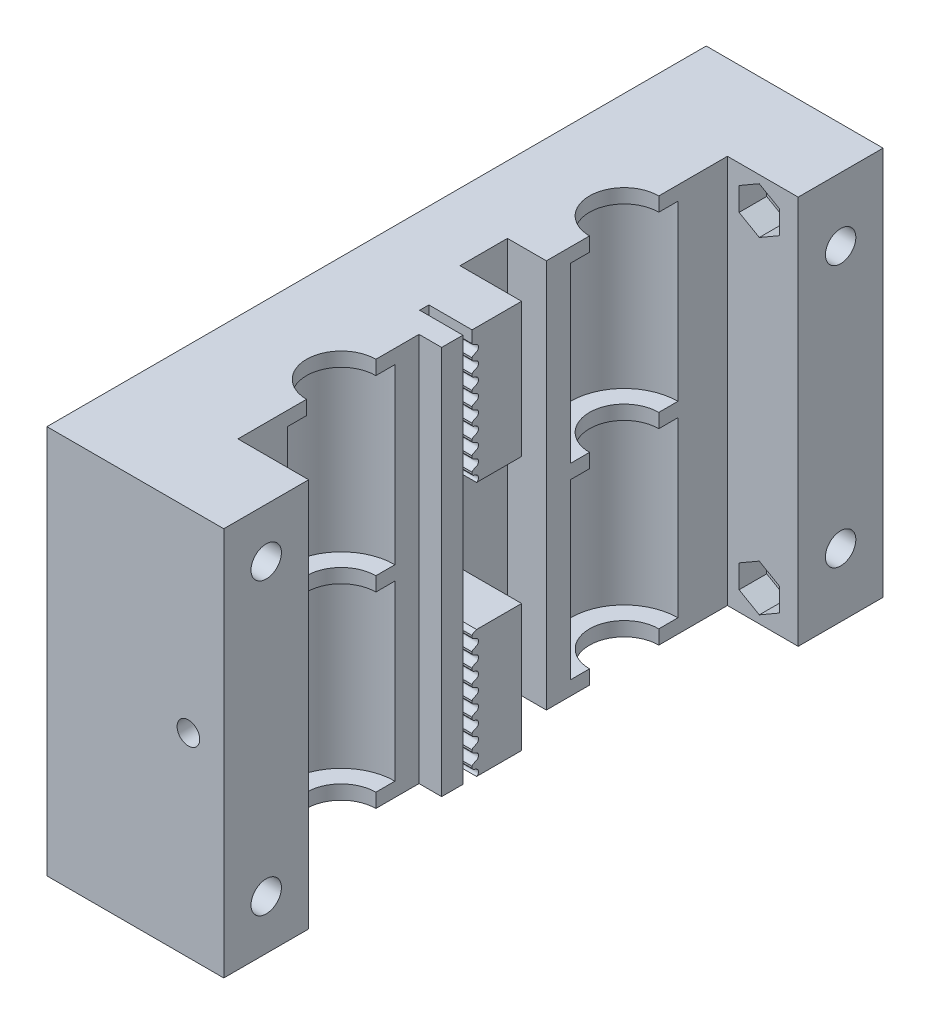
SolidWorks part; units mm, degrees
ref_plane "Front Plane" through (0, 0, 0) normal (0, 0, 1) x (1, 0, 0)
ref_plane "Top Plane" through (0, 0, 0) normal (0, 1, 0) x (1, 0, 0)
ref_plane "Right Plane" through (0, 0, 0) normal (1, 0, 0) x (0, 0, -1)
sketch "Sketch1" plane through (0, 0, 0) normal (0, 1, 0) x (1, 0, 0)
  line L0 (0, 36.6) -> (0, 43.6)
  line L1 (0, 43.6) -> (10, 43.6)
  line L2 (10, 43.6) -> (10, 55.6)
  line L3 (10, 55.6) -> (-15, 55.6)
  line L5 (-15, -37.6) -> (10, -37.6)
  line L6 (10, -37.6) -> (10, -25.6)
  line L7 (10, -25.6) -> (0, -25.6)
  line L8 (0, -25.6) -> (0, -18.6)
  line L9 (0, 21.4) -> (0, -3.4) construction
  line L10 (0, 18) -> (-5.5, 18)
  line L11 (-5.5, 18) -> (-5.5, 0)
  line L12 (-5.5, 0) -> (0, 0)
  line L24 (-15, 55.6) -> (-15, -37.6)
  line L25 (0, 0) -> (0, -3.4)
  line L26 (0, 18) -> (0, 21.4)
  arc A1 (0, 21.4) -> (0, 36.6) centre (0, 29) cw
  arc A2 (0, -18.6) -> (0, -3.4) centre (0, -11) cw
  dimension "D2" = 7.6
  dimension "D3" = 7.6
  dimension "D4" = 7
  dimension "D5" = 7
  dimension "D6" = 12
  dimension "D7" = 12
  dimension "D8" = 18
  dimension "D9" = 10
  dimension "D10" = 10
  dimension "D11" = 5.5
  dimension "D12" = 3.4
  dimension "D13" = 3.4
  dimension "D14" = 25
  dimension "D15" = 40
extrude "Boss-Extrude1" add sketch "Sketch1" along normal blind 55
sketch "Sketch2" plane through (0, 0, 0) normal (0, -1, 0) x (1, 0, 0)
  line L0 (0, 18.6) -> (0, 15.9)
  line L1 (0, 6.1) -> (0, 3.4)
  line L2 (0, -21.4) -> (0, -24.102)
  line L3 (0, -33.898) -> (0, -36.6)
  arc A0 (0, 3.4) -> (0, 18.6) centre (0, 11) cw
  arc A1 (0, 6.1) -> (0, 15.9) centre (0, 11) cw
  arc A2 (0, -36.6) -> (0, -21.4) centre (0, -29) cw
  arc A3 (0, -33.898) -> (0, -24.102) centre (0, -29) cw
  dimension "D1" = 4.9
  dimension "D2" = 4.898
extrude "Boss-Extrude2" add sketch "Sketch2" against normal blind 2
ref_plane "Plane1" through (0, 26.5, 0) normal (0, -1, 0) x (-1, 0, 0)
sketch "Sketch3" plane through (0, 26.5, 0) normal (0, -1, 0) x (-1, 0, 0)
  line L0 (0, -3.4) -> (0, -6.1)
  line L1 (0, -15.9) -> (0, -18.6)
  line L2 (0, 21.4) -> (0, 24.1)
  line L3 (0, 33.9) -> (0, 36.6)
  arc A0 (0, -18.6) -> (0, -3.4) centre (0, -11) ccw
  arc A1 (0, -15.9) -> (0, -6.1) centre (0, -11) ccw
  arc A2 (0, 36.6) -> (0, 21.4) centre (0, 29) cw
  arc A3 (0, 24.1) -> (0, 33.9) centre (0, 29) ccw
  dimension "D1" = 4.9
extrude "Boss-Extrude3" add sketch "Sketch3" against normal blind 2
ref_plane "Plane2" through (0, 53, 0) normal (0, -1, 0) x (-1, 0, 0)
sketch "Sketch4" plane through (0, 53, 0) normal (0, -1, 0) x (-1, 0, 0)
  line L0 (0, -18.6) -> (0, -15.9)
  line L1 (0, -6.1) -> (0, -3.4)
  line L2 (0, 36.6) -> (0, 33.9)
  line L3 (0, 24.1) -> (0, 21.4)
  arc A0 (0, -3.4) -> (0, -18.6) centre (0, -11) cw
  arc A1 (0, -15.9) -> (0, -6.1) centre (0, -11) ccw
  arc A2 (0, -15.9) -> (0, -6.1) centre (0, -11) ccw construction
  arc A3 (0, 21.4) -> (0, 36.6) centre (0, 29) ccw construction
  arc A5 (0, 24.1) -> (0, 33.9) centre (0, 29) ccw
  arc A6 (0, 21.4) -> (0, 36.6) centre (0, 29) ccw
  arc A7 (0, 24.1) -> (0, 33.9) centre (0, 29) ccw construction
extrude "Boss-Extrude4" add sketch "Sketch4" against normal blind 2
sketch "Sketch7" plane through (0, 55, 0) normal (0, 1, 0) x (1, 0, 0)
  line L0 (0, 0) -> (3.2, 0)
  line L1 (3.2, 0) -> (3.2, -2)
  line L2 (3.2, -2) -> (0, -2)
  line L3 (0, -6.1) -> (0, 0) construction
  line L4 (0, -2) -> (0, 0)
  dimension "D1" = 2
  dimension "D2" = 3.2
extrude "Boss-Extrude5" add sketch "Sketch7" against normal up to surface (55 mm away) up to face at (-0.6749, 0, -9)
sketch "Sketch8" plane through (0, 55, 0) normal (0, 1, 0) x (1, 0, 0)
  line L0 (0, 18) -> (0, 0) construction
  line L1 (-3.9424, 9) -> (6.0186, 9) construction
  line L2 (-5.5, 0) -> (3.2, 0)
  line L3 (3.2, 0) -> (-5.5, 0) construction
  line L4 (3.2, 0) -> (3.2, 3)
  line L5 (3.2, 3) -> (-5.5, 3)
  line L6 (-5.5, 0) -> (-5.5, 18) construction
  line L7 (-5.5, 3) -> (-5.5, 0)
  line L8 (3.2, -2) -> (3.2, 0) construction
  line L9 (-5.5, 11.3) -> (3.2, 11.3)
  line L10 (3.2, 11.3) -> (3.2, 4.3)
  line L11 (3.2, 4.3) -> (-5.5, 4.3)
  line L12 (-5.5, 4.3) -> (-5.5, 11.3)
  point P6 (0, 9)
  dimension "D1" = 3
  dimension "D2" = 7
  dimension "D3" = 1.3
extrude "Boss-Extrude6" add sketch "Sketch8" against normal up to surface (55 mm away) up to face at (-0.2443, 0, -7.7778)
sketch "Sketch11" plane through (3.2, 0, 0) normal (1, 0, 0) x (0, 0, -1)
  line L0 (1264.5675, 560.6102) -> (1262.5675, 560.6102) construction
  line L1 (4.3, 0) -> (4.3, 55) construction
  line L2 (4.2853, 45.4328) -> (4.2853, 47.4569)
  spline S0 degree 3 poles (4.2853, 47.4569) (4.284, 47.4147) (4.2867, 47.3463) (4.3158, 47.2523) (4.3712, 47.1708) (4.4771, 47.1012) (4.6041, 47.0544) (4.7214, 46.9971) (4.8254, 46.9474) (4.9241, 46.9047) (5.0186, 46.8525) (5.1086, 46.7783) (5.1561, 46.6816) (5.1905, 46.5926) (5.1913, 46.5195) (5.1931, 46.4561) (5.1891, 46.3829) (5.1871, 46.2871) (5.1399, 46.1709) (5.0494, 46.057) (4.9087, 45.9856) (4.7554, 45.916) (4.621, 45.8529) (4.5075, 45.8004) (4.4122, 45.7562) (4.3028, 45.6419) (4.2855, 45.5136) (4.2853, 45.4328) knots 0 0 0 0 0.042789 0.068472 0.09859 0.140403 0.193951 0.235463 0.272242 0.310543 0.344117 0.381404 0.42616 0.451184 0.477135 0.499165 0.515432 0.551275 0.595353 0.639476 0.695379 0.752126 0.810504 0.845135 0.878871 0.916023 1 1 1 1
  line M5 (4.3, 55) -> (4.3, 0)
  dimension "D1" = 2
extrude "Cut-Extrude4" cut sketch "Sketch11" against normal up to surface (8.7 mm away) contours S0 M5 region at (3.2, 46.4474, -4.673) up to face at (-5.5, 27.5, -3.65)
pattern_linear "LPattern1" count 24 spacing 2 along (0, -1, 0) count 4 spacing 2 along (0, 1, 0) of "Cut-Extrude4"
sketch "Sketch12" plane through (3.2, 0, 0) normal (1, 0, 0) x (0, 0, -1)
  line L0 (11.3, 0) -> (11.3, 55) construction
  line L1 (11.3, 36) -> (4.3, 36)
  line L2 (11.3, 36) -> (11.3, 18)
  line L3 (11.3, 18) -> (4.3, 18)
  line L4 (4.3, 36) -> (4.3, 18)
  dimension "D1" = 18
  dimension "D2" = 19
extrude "Cut-Extrude5" cut sketch "Sketch12" against normal up to surface (8.7 mm away) up to face at (-5.5, 27.5, -14.65)
sketch "Sketch13" plane through (0, 55, 0) normal (0, 1, 0) x (1, 0, 0)
  line L0 (-5.5, 3) -> (-2.9059, 3)
  line L1 (3.2, 3) -> (-5.5, 3) construction
  line L6 (-2.9059, 3) -> (-2.9059, 7.169)
  line L7 (-2.9059, 7.169) -> (-5.5, 7.169)
  line L8 (-5.5, 18) -> (-5.5, 0) construction
  line L9 (-5.5, 7.169) -> (-5.5, 3)
extrude "Boss-Extrude16" add sketch "Sketch13" against normal up to surface (55 mm away) up to face at (-0.409, 0, -8.1123)
sketch "Sketch14" plane through (0, 55, 0) normal (0, 1, 0) x (1, 0, 0)
  line L0 (0, 0) -> (0, -2)
  line L1 (0, -2) -> (3.2, -2)
  line L2 (3.2, -2) -> (3.2, 0)
  line L3 (3.2, -2) -> (3.2, 3) construction
  line L4 (3.2, 0) -> (0, 0)
extrude "Cut-Extrude6" cut sketch "Sketch14" against normal up to surface (55 mm away) up to face at (-0.1732, 0, -8.1123)
sketch "Sketch16" plane through (-2.9059, 0, 0) normal (1, 0, 0) x (0, 0, -1)
  line L0 (7.169, 36) -> (3, 36)
  line L1 (3, 0) -> (3, 55) construction
  line L2 (7.169, 18) -> (3, 18)
  line L3 (3, 18) -> (3, 36)
  line L4 (7.169, 36) -> (7.169, 18)
extrude "Cut-Extrude7" cut sketch "Sketch16" against normal up to surface (2.5941 mm away) up to face at (-5.5, 27.25, -11.9423)
sketch "Sketch17" plane through (-15, 0, 0) normal (-1, 0, 0) x (0, 0, 1)
  line L0 (-55.6, 55) -> (37.6, 55) construction
  line L1 (37.6, 55) -> (37.6, 0) construction
  line L2 (37.6, 0) -> (25.6, 0) construction
  line L3 (-36.6, 0) -> (-43.6, 0) construction
  line L4 (-55.6, 55) -> (-55.6, 0) construction
  circle A0 centre (31.6, 48) radius 2.15
  circle A1 centre (31.6, 7) radius 2.15
  circle A2 centre (-49.6, 9) radius 2.15
  circle A3 centre (-49.6, 46) radius 2.15
  dimension "D1" = 4.3
  dimension "D2" = 4.3
  dimension "D3" = 4.3
  dimension "D4" = 4.3
  dimension "D6" = 6
  dimension "D7" = 7
  dimension "D5" = 7
  dimension "D8" = 6
  dimension "D9" = 9
  dimension "D10" = 6
  dimension "D11" = 6
  dimension "D12" = 9
extrude "Cut-Extrude8" cut sketch "Sketch17" against normal up to surface (25 mm away) up to face at (10, 27.5, 31.6)
ref_plane "Plane3" through (-11.9, 0, 0) normal (-1, 0, 0) x (0, 0, 1)
sketch "Sketch20" plane through (-5.5, 0, 0) normal (1, 0, 0) x (0, 0, -1)
  line L0 (55.6, 55) -> (-37.6, 55) construction
  line L1 (55.6, 55) -> (55.6, 0) construction
  circle A0 centre (7, 27.5) radius 2.7
  dimension "D1" = 5.4
  dimension "D2" = 27.5
  dimension "D3" = 48.6
extrude "Cut-Extrude9" cut sketch "Sketch20" against normal up to surface (9.5 mm away) up to face at (-15, 46, -47.45)
sketch "Sketch21" plane through (0, 0, -43.6) normal (0, 0, 1) x (1, 0, 0)
  line L0 (10, 55) -> (10, 0) construction
  line L1 (4.5, 47.3091) -> (7.35, 48.9546)
  line L2 (7.35, 48.9546) -> (7.35, 52.2454)
  line L3 (7.35, 52.2454) -> (4.5, 53.8909)
  line L4 (4.5, 53.8909) -> (1.65, 52.2454)
  line L5 (1.65, 52.2454) -> (1.65, 48.9546)
  line L6 (1.65, 48.9546) -> (4.5, 47.3091)
  line L7 (0, 55) -> (10, 55) construction
  circle A0 centre (4.5, 50.6) radius 2.85 construction
  dimension "D2" = 4.4
  dimension "D3" = 5.5
  dimension "D1" = 5.7
ref_plane "Plane4" through (0, 27.5, 0) normal (0, 1, 0) x (1, 0, 0)
extrude "Cut-Extrude10" cut sketch "Sketch21" against normal blind 3.9
sketch "Sketch23" plane through (0, 0, -47.5) normal (0, 0, 1) x (1, 0, 0)
  line L0 (0, 55) -> (10, 55) construction
  line L1 (10, 55) -> (10, 0) construction
  circle A0 centre (4.5, 50.6) radius 1.6
  dimension "D1" = 3.2
  dimension "D2" = 4.4
  dimension "D3" = 5.5
extrude "Cut-Extrude11" cut sketch "Sketch23" against normal up to surface (8.1 mm away) up to face at (-2.5, 27.5, -55.6)
mirror "Mirror1" about plane through (0, 27.5, 0) normal (0, 1, 0) of "Cut-Extrude11", "Cut-Extrude10"
sketch "Sketch26" plane through (0, 0, 25.6) normal (0, 0, -1) x (-1, 0, 0)
  line L0 (-10, 55) -> (-10, 0) construction
  line L1 (-5, 24.2091) -> (-2.15, 25.8546)
  line L2 (-2.15, 25.8546) -> (-2.15, 29.1454)
  line L3 (-2.15, 29.1454) -> (-5, 30.7909)
  line L4 (-5, 30.7909) -> (-7.85, 29.1454)
  line L5 (-7.85, 29.1454) -> (-7.85, 25.8546)
  line L6 (-7.85, 25.8546) -> (-5, 24.2091)
  line L7 (-10, 0) -> (0, 0) construction
  circle A0 centre (-5, 27.5) radius 2.85 construction
  dimension "D1" = 27.5
  dimension "D2" = 5
  dimension "D3" = 5.7
extrude "Cut-Extrude12" cut sketch "Sketch26" against normal blind 4
sketch "Sketch27" plane through (0, 0, 29.6) normal (0, 0, -1) x (-1, 0, 0)
  line L0 (-10, 55) -> (-10, 0) construction
  line L1 (-10, 55) -> (0, 55) construction
  circle A0 centre (-5, 27.5) radius 1.6
  dimension "D3" = 3.2
  dimension "D1" = 5
  dimension "D2" = 27.5
extrude "Cut-Extrude13" cut sketch "Sketch27" against normal up to surface (8 mm away) up to face at (-2.5, 27.5, 37.6)
sketch "Sketch28" plane through (-15, 0, 0) normal (-1, 0, 0) x (0, 0, 1)
  line L0 (-55.6, 55) -> (-55.6, 0) construction
  line L1 (-45.95, 11.1073) -> (-49.6, 13.2147)
  line L2 (-49.6, 13.2147) -> (-53.25, 11.1073)
  line L3 (-53.25, 11.1073) -> (-53.25, 6.8927)
  line L4 (-53.25, 6.8927) -> (-49.6, 4.7853)
  line L5 (-49.6, 4.7853) -> (-45.95, 6.8927)
  line L6 (-45.95, 6.8927) -> (-45.95, 11.1073)
  circle A0 centre (-49.6, 9) radius 3.65 construction
  dimension "D1" = 7.3
extrude "Cut-Extrude14" cut sketch "Sketch28" against normal blind 4
pattern_linear "LPattern4" count 2 spacing 37 along (0, 1, 0) of "Cut-Extrude14"
sketch "Sketch29" plane through (-15, 0, 0) normal (-1, 0, 0) x (0, 0, 1)
  line L0 (37.6, 55) -> (37.6, 0) construction
  line L1 (31.6, 11.2147) -> (27.95, 9.1073)
  line L2 (27.95, 9.1073) -> (27.95, 4.8927)
  line L3 (27.95, 4.8927) -> (31.6, 2.7853)
  line L4 (31.6, 2.7853) -> (35.25, 4.8927)
  line L5 (35.25, 4.8927) -> (35.25, 9.1073)
  line L6 (35.25, 9.1073) -> (31.6, 11.2147)
  circle A0 centre (31.6, 7) radius 3.65 construction
  point P11 (35.25, 7)
  dimension "D1" = 7.3
extrude "Cut-Extrude15" cut sketch "Sketch29" against normal blind 4
pattern_linear "LPattern5" count 2 spacing 41 along (0, 1, 0) of "Cut-Extrude15"
ref_plane "Plane5" through (0, 0, -53.7) normal (0, 0, -1) x (-1, 0, 0)
